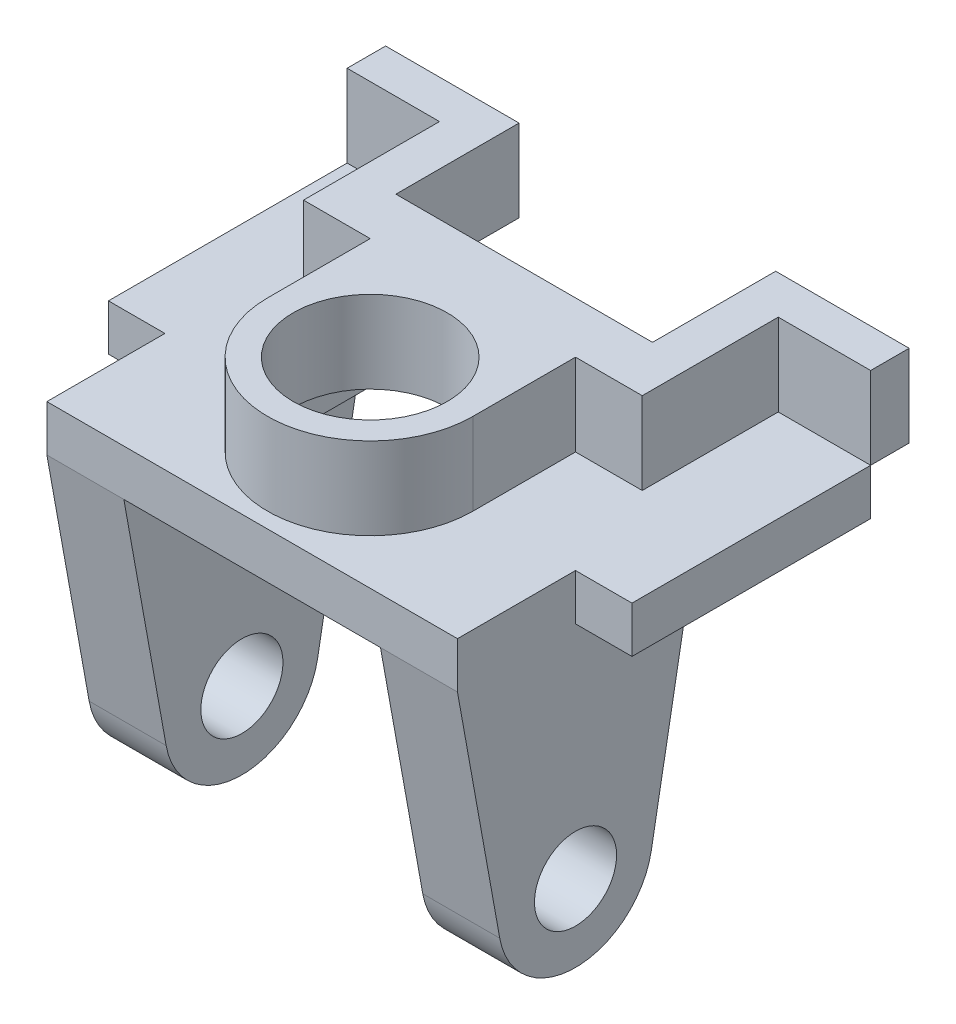
SolidWorks part; units mm, degrees
ref_plane "Front Plane" through (0, 0, 0) normal (0, 0, 1) x (1, 0, 0)
ref_plane "Top Plane" through (0, 0, 0) normal (0, 1, 0) x (1, 0, 0)
ref_plane "Right Plane" through (0, 0, 0) normal (1, 0, 0) x (0, 0, -1)
sketch "Sketch1" plane through (0, 0, 0) normal (0, 1, 0) x (1, 0, 0)
  line L0 (0, 0) -> (-30143.6644, 0) construction
  line L1 (0, 0) -> (0, -30143.6644) construction
  line L2 (40, 0) -> (40, 40)
  line L3 (40, 40) -> (66, 40)
  line L4 (66, 40) -> (66, 93)
  line L5 (66, 93) -> (102, 93)
  line L6 (102, 93) -> (102, 108)
  line L7 (102, 108) -> (50, 108)
  line L8 (50, 108) -> (50, 60)
  line L9 (50, 60) -> (-50, 60)
  line L10 (-50, 108) -> (-50, 60)
  line L11 (-102, 108) -> (-50, 108)
  line L12 (-102, 93) -> (-102, 108)
  line L13 (-66, 93) -> (-102, 93)
  line L14 (-66, 40) -> (-66, 93)
  line L15 (-40, 40) -> (-66, 40)
  line L16 (-40, 0) -> (-40, 40)
  line L17 (102, 93) -> (102, 0)
  line L18 (102, 0) -> (80, 0)
  line L19 (80, 0) -> (80, -46)
  line L20 (80, -46) -> (-80, -46)
  line L21 (-80, 0) -> (-80, -46)
  line L22 (-102, 0) -> (-80, 0)
  line L23 (-102, 93) -> (-102, 0)
  arc A0 (-40, 0) -> (40, 0) centre (0, 0) ccw
  circle A1 centre (0, 0) radius 30
  point P18 (0, 60)
  point P28 (0, 0)
  point P30 (0, -46)
  dimension "D1" = 80
  dimension "D2" = 60
  dimension "D3" = 60
  dimension "D4" = 48
  dimension "D5" = 52
  dimension "D6" = 15
  dimension "D7" = 36
  dimension "D8" = 100
  dimension "D9" = 40
  dimension "D10" = 46
extrude "Boss-Extrude1" add sketch "Sketch1" along normal blind 32 contours L16 A0 L2 L3 L4 L5 L6 L7 L8 L9 L10 L11 L12 L13 L14 L15 A1 region at (0, 0, -48.0109)
extrude "Boss-Extrude2" add sketch "Sketch1<3>" against normal blind 18 separate body contours A0 L16 L15 L14 L13 L23 L22 L21 L20 L19 L18 L17 L5 L4 L3 L2 region at (42.4685, 0, -20)
sketch "Sketch1<3>" plane through (0, 0, 0) normal (0, 1, 0) x (1, 0, 0) same geometry as "Sketch1"
sketch "Sketch2" plane through (80, 0, 0) normal (1, 0, 0) x (0, 0, -1)
  line L0 (0, -18) -> (-46, -18) construction
  line L1 (0, -18) -> (0, 0) construction
  line L2 (-46, -18) -> (-29.5234, -109.3264)
  line L3 (0, -104) -> (0, -47.8124) construction
  line L4 (46, -18) -> (29.5234, -109.3264)
  line L5 (-46, -18) -> (46, -18)
  circle A0 centre (0, -104) radius 16
  arc A1 (-29.5234, -109.3264) -> (29.5234, -109.3264) centre (0, -104) ccw
  dimension "D1" = 32
  dimension "D2" = 60
  dimension "D3" = 86
extrude "Boss-Extrude3" add sketch "Sketch2" against normal blind 30
mirror "Mirror1" about plane through (0, 0, 0) normal (1, 0, 0) of "Boss-Extrude3"
